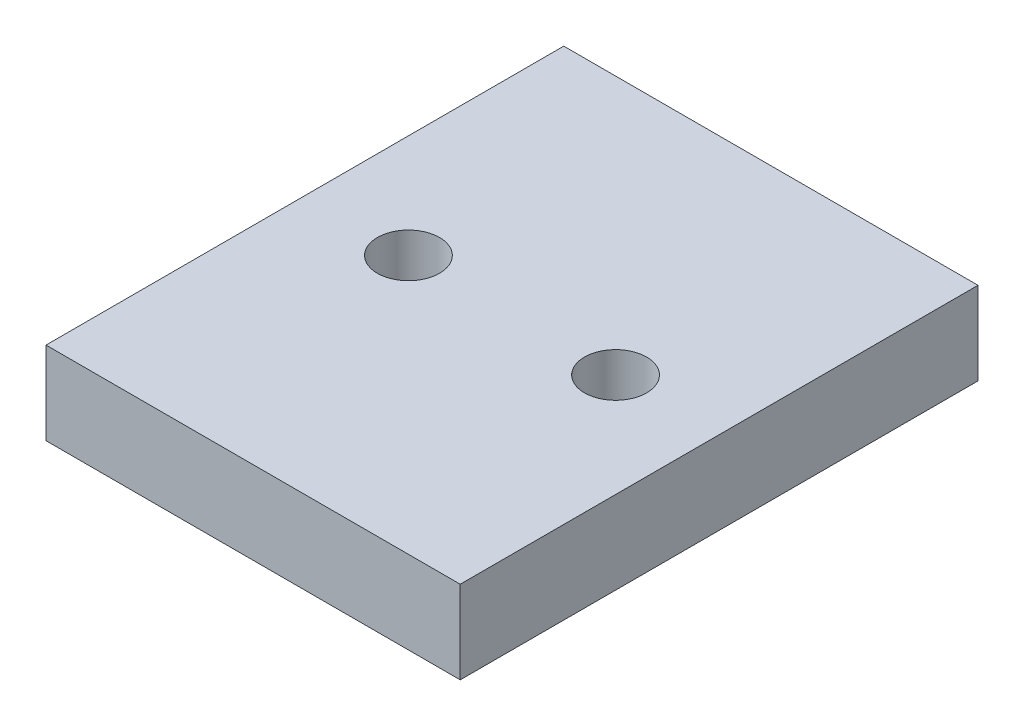
SolidWorks part; units mm, degrees
ref_plane "Front Plane" through (0, 0, 0) normal (0, 0, 1) x (1, 0, 0)
ref_plane "Top Plane" through (0, 0, 0) normal (0, 1, 0) x (1, 0, 0)
ref_plane "Right Plane" through (0, 0, 0) normal (1, 0, 0) x (0, 0, -1)
sketch "Sketch2" plane through (0, 0, 0) normal (1, 0, 0) x (0, 0, -1)
  line L0 (0, 0) -> (25, 0)
  line L4 (25, 4) -> (0, 4)
  line L7 (0, 4) -> (0, 0)
  line L8 (25, 0) -> (25, 4)
  dimension "D2" = 4
  dimension "D3" = 25
extrude "ProfileBoss-Extrude1" add sketch "Sketch2" along normal blind 20
sketch "MountHolesSketch5" plane through (0, 4, 0) normal (0, 1, 0) x (1, 0, 0)
  line L0 (0, 25) -> (0, 0) construction
  line L1 (20, 25) -> (20, 0) construction
  line L3 (20, 0) -> (0, 0) construction
  circle A0 centre (5, 12.5) radius 1.5
  circle A1 centre (15, 12.5) radius 1.5
  dimension "D1" = 3
  dimension "D2" = 5
  dimension "D4" = 12.5
  dimension "D3" = 5
extrude "MountHolesCut-Extrude2" cut sketch "MountHolesSketch5" against normal through all
equation "\"ChannelRiserHeight\"= 4mm"
equation "\"D2@Sketch2\"=\"ChannelRiserHeight\""
equation "\"ChannelWidth\"= 25mm"
equation "\"ChannelLength\"= 20mm"
equation "\"D1@ProfileBoss-Extrude1\"=\"ChannelLength\""
equation "\"D3@Sketch2\"=\"ChannelWidth\""
equation "\"D4@MountHolesSketch5\"=\"ChannelWidth\"/2"
equation "\"D2@MountHolesSketch5\"=\"ChannelLength\"/4"
equation "\"D3@MountHolesSketch5\"=\"ChannelLength\"/4"
